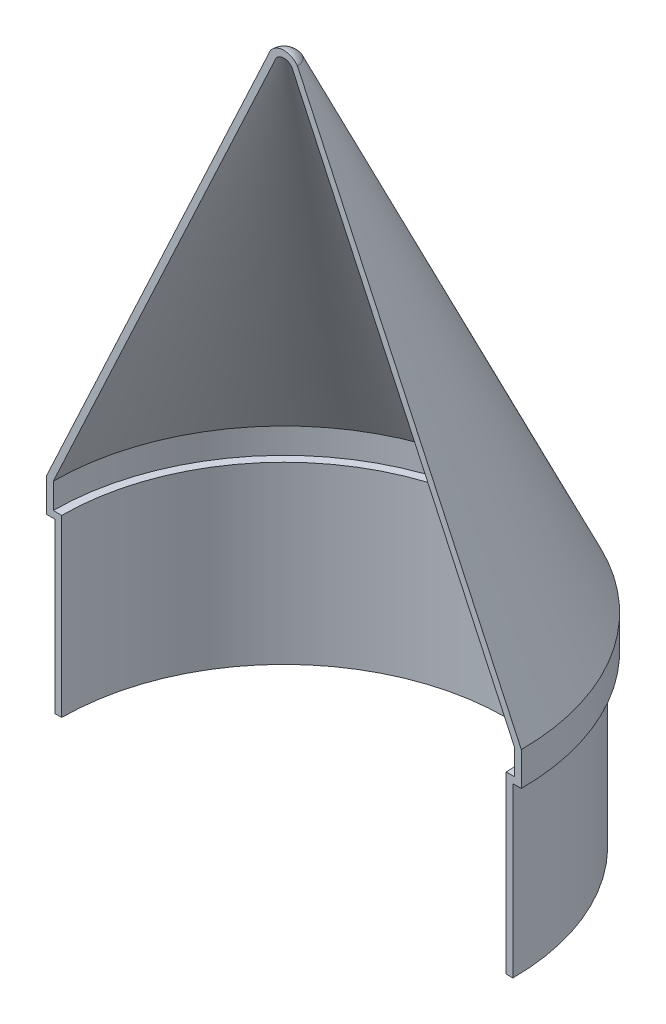
SolidWorks part; units mm, degrees
ref_plane "Front Plane" through (0, 0, 0) normal (0, 0, 1) x (1, 0, 0)
ref_plane "Top Plane" through (0, 0, 0) normal (0, 1, 0) x (1, 0, 0)
ref_plane "Right Plane" through (0, 0, 0) normal (1, 0, 0) x (0, 0, -1)
sketch "Sketch3" plane through (0, 0, 0) normal (0, 0, 1) x (1, 0, 0)
  line L1 (0, 0) -> (0, 154.6097)
  line L4 (0, 0) -> (0, -50)
  line L5 (0, -50) -> (68, -50)
  line L6 (68, -50) -> (68, 0)
  line L9 (70.5, 0) -> (70.5, 10)
  line L11 (68, 0) -> (70.5, 0)
  line L12 (4, 152.6097) -> (70.5, 10)
  line L13 (0, 229.1763) -> (0, 65.794) construction
  arc A0 (0, 154.6097) -> (4, 152.6097) centre (0, 149.6097) cw
  point P11 (68, -50)
  point P14 (70.5, 10)
  dimension "D1" = 25
  dimension "D2" = 136
  dimension "D3" = 2
  dimension "D4" = 141
  dimension "D5" = 8
  dimension "D6" = 10
  dimension "D7" = 50
revolve "Revolve1" add sketch "Sketch3" angle 360 about L1
shell "Shell1" thickness 2 removed face at (0, -50, -68)
sketch "Sketch4" plane through (0, 0, 0) normal (0, 0, 1) x (1, 0, 0)
  line L0 (68, -50) -> (-68, -50)
  line L1 (68, -50) -> (-68, -50)
  line L2 (-68, -50) -> (-68, 0)
  line L3 (-68, -50) -> (-68, 0)
  line L4 (-68, 0) -> (-70.5, 0)
  line L5 (-68, 0) -> (-70.5, 0)
  line L6 (-70.5, 0) -> (-70.5, 10)
  line L7 (-70.5, 0) -> (-70.5, 10)
  line L8 (-70.5, 10) -> (-4, 152.6097)
  line L9 (-70.5, 10) -> (-4, 152.6097)
  line L10 (4, 152.6097) -> (70.5, 10)
  line L11 (4, 152.6097) -> (70.5, 10)
  line L12 (70.5, 10) -> (70.5, 0)
  line L13 (70.5, 10) -> (70.5, 0)
  line L14 (70.5, 0) -> (68, 0)
  line L15 (70.5, 0) -> (68, 0)
  line L16 (68, 0) -> (68, -50)
  line L17 (68, 0) -> (68, -50)
  arc A0 (4, 152.6097) -> (-4, 152.6097) centre (0, 149.6097) ccw
  arc A1 (4, 152.6097) -> (-4, 152.6097) centre (0, 149.6097) ccw
extrude "Cut-Extrude1" cut sketch "Sketch4" along normal through all
